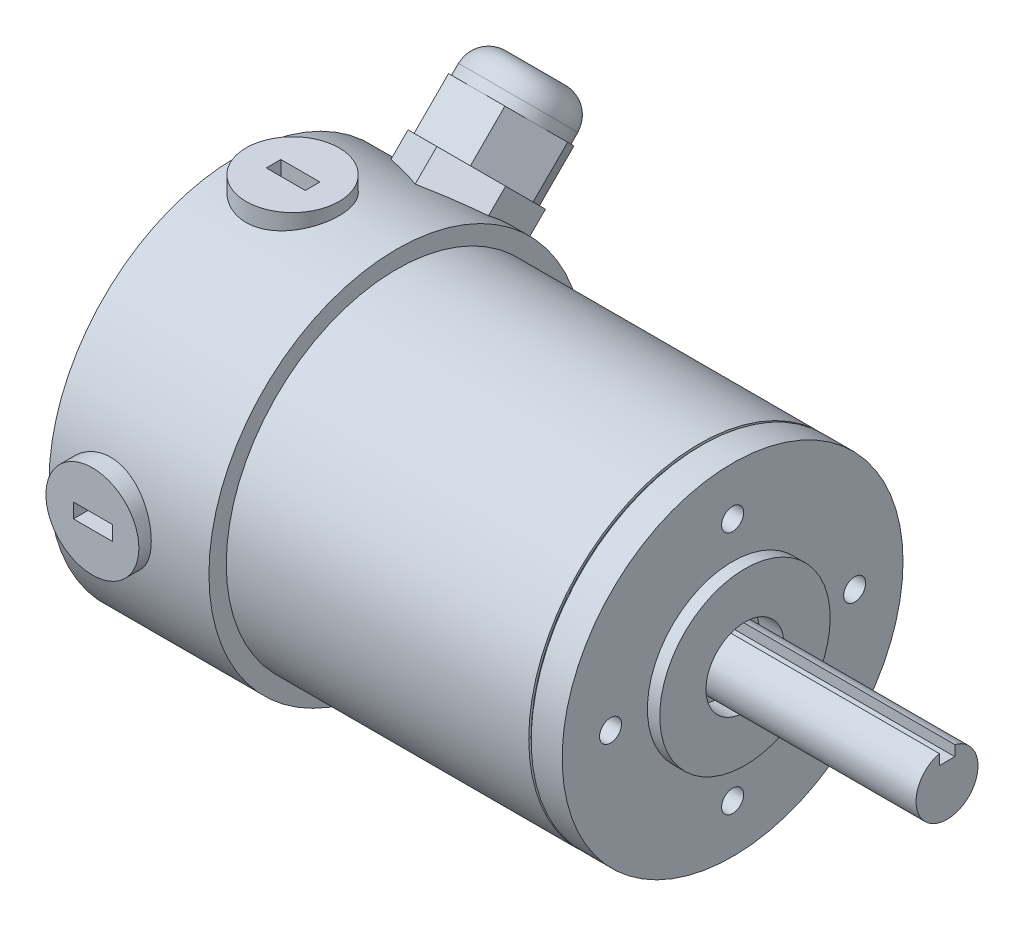
SolidWorks part; units mm, degrees
note: '?' marks a value the reader was unsure of.
ref_plane "Front" through (0, 0, 0) normal (0, 0, 1) x (1, 0, 0)
ref_plane "Top" through (0, 0, 0) normal (0, 1, 0) x (1, 0, 0)
ref_plane "Right" through (0, 0, 0) normal (1, 0, 0) x (0, 0, -1)
sketch "Sketch1" plane through (0, 0, 0) normal (1, 0, 0) x (0, 0, -1)
  circle A0 centre (0, 0) radius 34.925
  dimension "D1" = 69.85
extrude "Base-Extrude" add sketch "Sketch1" against normal blind 6.35
sketch "Sketch2" plane through (-6.35, 0, 0) normal (-1, 0, 0) x (0, 0, 1)
  circle A0 centre (0, 0) radius 34.425
  dimension "D1" = 68.85
extrude "Boss-Extrude3" add sketch "Sketch2" along normal blind 0.5
sketch "Sketch4" plane through (-6.85, 0, 0) normal (-1, 0, 0) x (0, 0, 1)
  circle A0 centre (0, 0) radius 34.925
  dimension "D1" = 69.85
extrude "Boss-Extrude4" add sketch "Sketch4" along normal blind 61.984
sketch "Sketch5" plane through (0, 0, 0) normal (1, 0, 0) x (0, 0, -1)
  circle A0 centre (0, 0) radius 17.4625
  dimension "D1" = 34.925
extrude "Boss-Extrude5" add sketch "Sketch5" along normal blind 2.54
sketch "Sketch6" plane through (2.54, 0, 0) normal (1, 0, 0) x (0, 0, -1)
  circle A0 centre (0, 0) radius 8
  dimension "D1" = 16
extrude "Cut-Extrude1" cut sketch "Sketch6" against normal blind 5.08
sketch "Sketch7" plane through (-2.54, 0, 0) normal (1, 0, 0) x (0, 0, -1)
  line L0 (-1.588, 6.1482) -> (-1.588, 4)
  line L1 (-1.588, 4) -> (1.5875, 4)
  line L2 (1.5875, 4) -> (1.5875, 6.1484)
  arc A0 (-1.588, 6.1482) -> (1.5875, 6.1484) centre (0, 0) ccw
  dimension "D4" = 6.35
  dimension "D1" = 1.5875
  dimension "D2" = 1.588
  dimension "D3" = 4
extrude "Boss-Extrude6" add sketch "Sketch7" along normal blind 46.482
sketch "Sketch8" plane through (-68.834, 0, 0) normal (-1, 0, 0) x (0, 0, 1)
  circle A0 centre (0, 0) radius 38.481
  dimension "D1" = 76.962
extrude "Boss-Extrude7" add sketch "Sketch8" along normal blind 32.766
sketch "Sketch9" plane through (-101.6, 0, 0) normal (-1, 0, 0) x (0, 0, 1)
  circle A0 centre (0, 0) radius 8
  dimension "D1" = 16
extrude "Cut-Extrude2" cut sketch "Sketch9" against normal blind 2.54
sketch "Sketch10" plane through (-99.06, 0, 0) normal (-1, 0, 0) x (0, 0, 1)
  circle A0 centre (0, 0) radius 6.35
  dimension "D1" = 12.7
extrude "Boss-Extrude8" add sketch "Sketch10" along normal blind 20.828
sketch "Sketch11" plane through (0, 0, 0) normal (0, 1, 0) x (1, 0, 0)
  line L0 (-99.06, 6.35) -> (-119.888, 6.35) construction
  line L1 (-101.6, 38.481) -> (-101.6, -38.481) construction
  circle A0 centre (-90.17, 0) radius 9.525
  dimension "D3" = 19.05
  dimension "D1" = 6.35
  dimension "D2" = 11.43
extrude "Boss-Extrude9" add sketch "Sketch11" along normal mid plane 82.042
sketch "Sketch12" plane through (0, 0, 0) normal (0, 0, 1) x (1, 0, 0)
  line L0 (-101.6, 0) -> (-68.834, 0) construction
  line L2 (-80.645, 38.481) -> (-80.645, 41.021) construction
  circle A0 centre (-90.17, 0) radius 9.525
  dimension "D2" = 19.05
  dimension "D1" = 9.525
extrude "Boss-Extrude10" add sketch "Sketch12" along normal mid plane 82.042
sketch "Sketch14" plane through (0, 41.021, 0) normal (0, 1, 0) x (-1, 0, 0)
  line L2 (86.0627, -1.5) -> (94.0627, -1.5)
  line L3 (86.0627, -1.5) -> (86.0627, 1.5)
  line L4 (86.0627, 1.5) -> (94.0627, 1.5)
  line L5 (94.0627, -1.5) -> (94.0627, 1.5)
  line L6 (99.695, -6.35) -> (119.888, -6.35) construction
  dimension "D1" = 8
  dimension "D2" = 3
  dimension "D3" = 4.85
extrude "Cut-Extrude3" cut sketch "Sketch14" against normal blind 4
sketch "Sketch15" plane through (0, -41.021, 0) normal (0, -1, 0) x (1, 0, 0)
  line L1 (-86.0627, 1.5) -> (-94.0627, 1.5)
  line L2 (-86.0627, 1.5) -> (-86.0627, -1.5)
  line L3 (-86.0627, -1.5) -> (-94.0627, -1.5)
  line L4 (-94.0627, 1.5) -> (-94.0627, -1.5)
extrude "Cut-Extrude4" cut sketch "Sketch15" against normal blind 4
sketch "Sketch16" plane through (0, 0, 41.021) normal (0, 0, 1) x (1, 0, 0)
  line L0 (-86.0627, -37.021) -> (-86.0627, -41.021) construction
  line L1 (-94.0627, 1.5) -> (-86.0627, 1.5)
  line L2 (-94.0627, 1.5) -> (-94.0627, -1.5)
  line L3 (-94.0627, -1.5) -> (-86.0627, -1.5)
  line L4 (-86.0627, 1.5) -> (-86.0627, -1.5)
  line L5 (-119.888, -6.35) -> (-99.695, -6.35) construction
  dimension "D1" = 3
  dimension "D2" = 8
  dimension "D3" = 8
  dimension "D4" = 4.85
extrude "Cut-Extrude5" cut sketch "Sketch16" against normal blind 4
sketch "Sketch17" plane through (0, 0, -41.021) normal (0, 0, -1) x (-1, 0, 0)
  line L1 (86.0627, 1.5) -> (94.0627, 1.5)
  line L2 (86.0627, 1.5) -> (86.0627, -1.5)
  line L3 (86.0627, -1.5) -> (94.0627, -1.5)
  line L4 (94.0627, 1.5) -> (94.0627, -1.5)
extrude "Cut-Extrude6" cut sketch "Sketch17" against normal blind 4
sketch "Sketch18" plane through (0, 0, 0) normal (1, 0, 0) x (0, 0, -1)
  circle A1 centre (0, 25.019) radius 2.25
  circle A2 centre (25.019, 0) radius 2.25
  circle A3 centre (0, -25.019) radius 2.25
  circle A4 centre (-25.019, 0) radius 2.25
  dimension "D1" = 25.019
  dimension "D6" = 4.5
  dimension "D7" = 4.5
  dimension "D8" = 4.5
  dimension "D9" = 4.5
  dimension "D2" = 25.019
  dimension "D3" = 25.019
  dimension "D4" = 25.019
  dimension "D5" = 35.3822
extrude "Cut-Extrude7" cut sketch "Sketch18" against normal blind 12.7
ref_axis "Axis1" through (-119.888, 0, 0) along (1, 0, 0)?
ref_plane "Plane3" through (0, 0, 0) normal (0, 0.7071, -0.7071) x (-1, 0, 0)
sketch "Sketch21" plane through (0, 0, 0) normal (0, 0.7071, -0.7071) x (-1, 0, 0)
  line L0 (119.888, 6.35) -> (99.06, 6.35) construction
  line L1 (82.834, -11.547) -> (92.834, -5.7735)
  line L2 (92.834, -5.7735) -> (92.834, 5.7735)
  line L3 (92.834, 5.7735) -> (82.834, 11.547)
  line L4 (82.834, 11.547) -> (72.834, 5.7735)
  line L5 (72.834, 5.7735) -> (72.834, -5.7735)
  line L6 (72.834, -5.7735) -> (82.834, -11.547)
  line L7 (68.834, 38.481) -> (68.834, -38.481) construction
  circle A0 centre (82.834, 0) radius 10 construction
  dimension "D1" = 6.35
  dimension "D2" = 20
  dimension "D3" = 4
extrude "Boss-Extrude12" add sketch "Sketch21" along normal blind 43
sketch "Sketch22" plane through (0, 30.4056, -30.4056) normal (0, 0.7071, -0.7071) x (-1, 0, 0)
  line L0 (101.6, 0) -> (68.834, 0) construction
  line L1 (88.6075, 10) -> (77.0605, 10)
  line L2 (77.0605, 10) -> (71.287, 0)
  line L3 (71.287, 0) -> (77.0605, -10)
  line L4 (77.0605, -10) -> (88.6075, -10)
  line L5 (88.6075, -10) -> (94.381, 0)
  line L6 (94.381, 0) -> (88.6075, 10)
  circle A0 centre (82.834, 0) radius 10 construction
  dimension "D1" = 20
extrude "Boss-Extrude13" add sketch "Sketch22" along normal blind 10
sketch "Sketch23" plane through (0, 37.4767, -37.4767) normal (0, 0.7071, -0.7071) x (-1, 0, 0)
  line L0 (101.6, 0) -> (68.834, 0) construction
  line L2 (88.6075, -10) -> (94.381, 0) construction
  circle A0 centre (82.834, 0) radius 10
  dimension "D2" = 20
  dimension "D1" = 10
extrude "Boss-Extrude14" add sketch "Sketch23" along normal blind 7
fillet "Fillet1" radius 5
